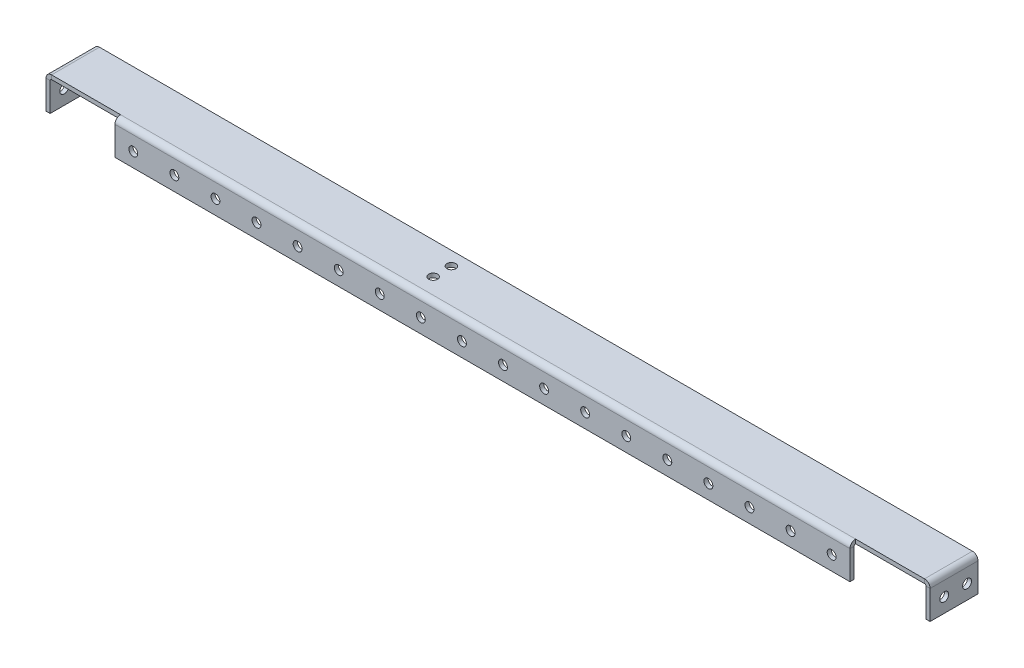
SolidWorks part; units mm, degrees
note: The reader was unsure of these and kept them because the rebuilt part matched: thickness of "Base-Flange1", "Edge-Flange2", "Edge-Flange3", "Edge-Flange1", "Sheet-Metal1", "Sheet-Metal2", "Sheet-Metal3", "Sheet-Metal4", "Sheet-Metal7", "Sheet-Metal8", "Sheet-Metal9", "Sheet-Metal10", "Sheet-Metal11"; flange length of "Edge-Flange2", "Edge-Flange3", "Edge-Flange1".
ref_plane "Front Plane" through (0, 0, 0) normal (0, 0, 1) x (1, 0, 0)
ref_plane "Top Plane" through (0, 0, 0) normal (0, 1, 0) x (1, 0, 0)
ref_plane "Right Plane" through (0, 0, 0) normal (1, 0, 0) x (0, 0, -1)
sketch "Sketch1" plane through (0, 0, 0) normal (0, 1, 0) x (1, 0, 0)
  line L1 (489.688, 0) -> (0, 0)
  line L2 (489.688, 0) -> (489.688, 26.67)
  line L3 (489.688, 26.67) -> (0, 26.67)
  line L4 (0, 0) -> (0, 26.67)
  point P0 (0, 0)
  dimension "D1" = 489.688
  dimension "D2" = 26.67
base flange "Base-Flange1" sketch "Sketch1" thickness 2.286 reverse thickness direction no parameters "D1"=0.8128
edge flange "Edge-Flange2" sketch "Sketch11" flange angle 90 flange length 19.05 flange position material inside bend radius 0.8128 thickness 2.286 relief rectangular parameters "D6"=10
sketch "Sketch11" plane through (0, -2.286, 0) normal (-1, 0, 0) x (0, 0, -1)
  line L0 (26.67, 0) -> (0, 0) construction
  line L1 (26.67, 0) -> (0, 0)
  line L2 (0, 0) -> (0, 16.764)
  line L3 (0, 16.764) -> (26.67, 16.764)
  line L4 (26.67, 16.764) -> (26.67, 0)
bend "EdgeBend2" bend radius 0.8128 bend angle 90 parameters "D5"=2
edge flange "Edge-Flange3" sketch "Sketch14" flange angle 90 flange length 19.05 flange position material outside bend radius 0.8128 thickness 2.286 relief rectangular parameters "D6"=10
sketch "Sketch14" plane through (489.688, -2.286, 0) normal (1, 0, 0) x (0, 0, 1)
  line L2 (-26.67, 0) -> (-26.67, 16.764)
  line L3 (-26.67, 16.764) -> (0, 16.764)
  line L4 (0, 16.764) -> (0, 0)
  line L7 (0, 0) -> (-26.67, 0) construction
  line L8 (0, 0) -> (-26.67, 0)
bend "EdgeBend3" bend radius 0.8128 bend angle 90 parameters "D5"=3
edge flange "Edge-Flange1" sketch "Sketch8" flange angle 90 flange length 19.05 flange position bend outside bend radius 0.8128 thickness 2.286 relief rectangular parameters "D6"=10
sketch "Sketch8" plane through (0, -2.286, 0) normal (0, 0, -1) x (1, 0, 0)
  line L0 (488.8752, 0) -> (3.0988, 0) construction
  line L2 (3.0988, 0) -> (3.0988, 16.764)
  line L3 (3.0988, 16.764) -> (488.8752, 16.764)
  line L4 (488.8752, 16.764) -> (488.8752, 0)
  line L5 (488.8752, 0) -> (3.0988, 0)
bend "EdgeBend1" bend radius 0.8128 bend angle 90 parameters "D5"=1
sketch "Sketch15" plane through (0, 0, 0.8128) normal (0, 0, -1) x (-1, 0, 0)
  line L0 (-488.8752, -19.05) -> (-3.0988, -19.05) construction
  line L1 (-59.436, -3.0988) -> (-21.336, -3.0988)
  line L2 (-59.436, -3.0988) -> (-59.436, -35.0012)
  line L3 (-59.436, -35.0012) -> (-21.336, -35.0012)
  line L4 (-21.336, -3.0988) -> (-21.336, -35.0012)
  line L5 (-59.436, -3.0988) -> (-21.336, -35.0012) construction
  line L6 (-59.436, -35.0012) -> (-21.336, -3.0988) construction
  line L7 (-488.8752, -3.0988) -> (-3.0988, -3.0988) construction
  line L8 (-2.286, -3.0988) -> (-2.286, -19.05) construction
  line L9 (-489.688, -19.05) -> (-489.688, -3.0988) construction
  line L10 (-479.528, -3.0988) -> (-441.428, -3.0988)
  line L11 (-479.528, -3.0988) -> (-479.528, -35.0012)
  line L12 (-479.528, -35.0012) -> (-441.428, -35.0012)
  line L13 (-441.428, -3.0988) -> (-441.428, -35.0012)
  line L14 (-479.528, -3.0988) -> (-441.428, -35.0012) construction
  line L15 (-479.528, -35.0012) -> (-441.428, -3.0988) construction
  point P0 (-40.386, -19.05)
  point P12 (-460.478, -19.05)
  dimension "D1" = 19.05
  dimension "D2" = 38.1
  dimension "D3" = 10.16
  dimension "D4" = 38.1
sketch "Sketch16" plane through (491.974, 0, 0) normal (1, 0, 0) x (0, 0, -1)
  line L0 (7.874, -11.0744) -> (33.274, -11.0744) construction
  line L2 (0, -3.0988) -> (0, -19.05) construction
  circle A0 centre (7.874, -11.0744) radius 2.4765
  circle A1 centre (20.574, -11.0744) radius 2.4765
  point P7 (0, -11.0744)
  dimension "D1" = 4.953
  dimension "D4" = 12.7
  dimension "D3" = 7.874
extrude "Cut-Extrude1" cut sketch "Sketch16" against normal through all normal cut yes
sketch "Sketch17" plane through (0, 0, 0.8128) normal (0, 0, -1) x (-1, 0, 0)
  line L1 (-3.0988, 0) -> (-41.4782, 0)
  line L2 (-3.0988, 0) -> (-3.0988, -19.05)
  line L3 (-3.0988, -19.05) -> (-41.4782, -19.05)
  line L4 (-41.4782, 0) -> (-41.4782, -19.05)
  line L5 (-488.8752, -19.05) -> (-3.0988, -19.05) construction
  line L6 (-3.0988, -19.05) -> (-3.0988, -3.0988) construction
  line L7 (-488.8752, -2.286) -> (-3.0988, -2.286) construction
  line L8 (-245.987, -2.286) -> (-245.987, -179.1808) construction
  line L9 (-488.8752, 0) -> (-488.8752, -19.05)
  line L10 (-450.4958, 0) -> (-450.4958, -19.05)
  line L11 (-488.8752, 0) -> (-450.4958, 0)
  line L12 (-488.8752, -19.05) -> (-450.4958, -19.05)
  line L13 (-488.8752, 0) -> (-3.0988, 0) construction
  point P10 (-245.987, -2.286)
  dimension "D1" = 38.3794
  dimension "D2" = 38.3794
extrude "Cut-Extrude2" cut sketch "Sketch17" along normal up to vertex (0.8128 mm away) and the other way blind 2.54 normal cut yes up to point (488.8752, -2.286, 0)
sketch "Sketch18" plane through (0, 0, 0.8128) normal (0, 0, -1) x (-1, 0, 0)
  line L0 (-245.987, -19.05) -> (-245.987, -3.0988) construction
  line L1 (-450.4958, -19.05) -> (-41.4782, -19.05) construction
  line L2 (-450.4958, -3.0988) -> (-41.4782, -3.0988) construction
  line L3 (-440.297, -11.0744) -> (-417.437, -11.0744) construction
  circle A0 centre (-440.297, -11.0744) radius 2.4765
  circle A1 centre (-417.437, -11.0744) radius 2.4765
  circle A2 centre (-394.577, -11.0744) radius 2.4765
  circle A3 centre (-371.717, -11.0744) radius 2.4765
  circle A4 centre (-348.857, -11.0744) radius 2.4765
  circle A5 centre (-325.997, -11.0744) radius 2.4765
  circle A6 centre (-303.137, -11.0744) radius 2.4765
  circle A7 centre (-280.277, -11.0744) radius 2.4765
  circle A8 centre (-257.417, -11.0744) radius 2.4765
  circle A9 centre (-234.557, -11.0744) radius 2.4765
  circle A10 centre (-211.697, -11.0744) radius 2.4765
  circle A11 centre (-188.837, -11.0744) radius 2.4765
  circle A12 centre (-165.977, -11.0744) radius 2.4765
  circle A13 centre (-143.117, -11.0744) radius 2.4765
  circle A14 centre (-120.257, -11.0744) radius 2.4765
  circle A21 centre (-97.397, -11.0744) radius 2.4765
  circle A22 centre (-74.537, -11.0744) radius 2.4765
  circle A23 centre (-51.677, -11.0744) radius 2.4765
  point P48 (-245.987, -11.0744)
  dimension "D1" = 4.953
  dimension "D3" = 22.86
  dimension "D2" = 18
extrude "Cut-Extrude3" cut sketch "Sketch18" against normal up to next normal cut yes
sketch "Sketch19" plane through (0, -2.286, 0) normal (0, -1, 0) x (1, 0, 0)
  circle A0 centre (206.5428, -19.0612) radius 2.4765
  circle A1 centre (206.5428, -8.9012) radius 2.4765
  circle A2 centre (206.5428, -8.9012) radius 2.4765 construction
  circle A3 centre (206.5428, -19.0612) radius 2.4765 construction
extrude "Cut-Extrude4" cut sketch "Sketch19" against normal up to next normal cut yes
sketch "Sketch20" plane through (0, 0, 0) normal (0, 1, 0) x (1, 0, 0)
  line L0 (108.1517, 31.2083) -> (133.9068, 10.2325)
  line L1 (133.9068, 10.2325) -> (142.0425, -15.3618)
  line L2 (142.0425, -15.3618) -> (163.021, -38.7726)
  line L3 (108.1517, 31.2083) -> (513.6538, 44.0224)
  line L4 (513.6538, 44.0224) -> (545.1159, -54.9552)
  line L5 (545.1159, -54.9552) -> (163.021, -38.7726)
extrude "Cut-Extrude5" [suppressed] cut sketch "Sketch20" against normal through all
sketch "Bend-Lines1" [suppressed] plane through (0, 0, 0) normal (0, 1, 0) x (1, 0, 0)
sketch "Bounding-Box1" [suppressed] plane through (0, 0, 0) normal (0, 1, 0) x (1, 0, 0)
sheet metal parameters "Sheet-Metal1" thickness 2.286 parameters "D1"=0.8128, "D7"=2.3622
flat pattern "Flat-Pattern1" [suppressed]
sketch "Bend-Lines2" plane through (0, 0, 0) normal (0, 1, 0) x (1, 0, 0)
sketch3d "Bounding-Box2" [suppressed]
  line L0 (489.688, 0, 0) -> (0, 0, 0) construction
  line L1 (489.688, 25.4, 0) -> (0, 25.4, 0) construction
  line L2 (489.688, 0, 0) -> (489.688, 25.4, 0) construction
  line L3 (0, 0, 0) -> (0, 25.4, 0) construction
sheet metal parameters "Sheet-Metal2" thickness 2.286 parameters "D1"=0.8128, "D7"=2.3622
flat pattern "Flat-Pattern1" [suppressed]
sketch "Bend-Lines2" plane through (0, 0, 0) normal (0, 1, 0) x (1, 0, 0)
  line L0 (-240.1218, -1909.4058) -> (242.484, -1909.4058) construction
  line L1 (-240.1218, -1909.4058) -> (242.484, -1909.4058) construction
  line L2 (245.2652, -1906.6246) -> (245.2652, -1868.5246) construction
  line L3 (-242.903, -1868.5246) -> (-242.903, -1906.6246) construction
  line L4 (245.2652, -1906.6246) -> (245.2652, -1868.5246) construction
  line L5 (-242.903, -1868.5246) -> (-242.903, -1906.6246) construction
sketch3d "Bounding-Box2" [suppressed]
  line L0 (262.3741, -1926.5147, 0) -> (-260.0119, -1926.5147, 0) construction
  line L1 (262.3741, -1868.5246, 0) -> (-260.0119, -1868.5246, 0) construction
  line L2 (262.3741, -1926.5147, 0) -> (262.3741, -1868.5246, 0) construction
  line L3 (-260.0119, -1926.5147, 0) -> (-260.0119, -1868.5246, 0) construction
bend of the flat pattern "Flatten-<EdgeBend1>1"
bend of the flat pattern "Flatten-<EdgeBend3>2"
bend of the flat pattern "Flatten-<EdgeBend2>2"
sketch "Sketch15-1" plane through (0, -2.3622, 1907.4647) normal (0, -1, 0) x (-1, 0, 0)
  line L1 (185.3318, -4.7222) -> (223.4318, -4.7222)
  line L2 (185.3318, -4.7222) -> (185.3318, -33.3778)
  line L3 (185.3318, -33.3778) -> (223.4318, -33.3778)
  line L4 (223.4318, -4.7222) -> (223.4318, -33.3778)
  line L5 (185.3318, -4.7222) -> (223.4318, -33.3778) construction
  line L6 (185.3318, -33.3778) -> (223.4318, -4.7222) construction
  line L8 (-262.3741, 38.9401) -> (260.0119, 38.9401) construction
  line L9 (-262.3741, 38.9401) -> (260.0119, 38.9401) construction
  line L10 (-234.684, -4.7222) -> (-196.584, -4.7222)
  line L11 (-234.684, -4.7222) -> (-234.684, -33.3778)
  line L12 (-234.684, -33.3778) -> (-196.584, -33.3778)
  line L13 (-196.584, -4.7222) -> (-196.584, -33.3778)
  line L14 (-234.684, -4.7222) -> (-196.584, -33.3778) construction
  line L15 (-234.684, -33.3778) -> (-196.584, -4.7222) construction
  point P0 (204.3818, -19.05)
  point P12 (-215.634, -19.05)
  dimension "D1" = 19.05
  dimension "D2" = 38.1
  dimension "D3" = 10.16
  dimension "D4" = 38.1
sketch "Sketch16-1" [suppressed] plane through (243.3241, 0, 0) normal (0, 1, 0) x (0, 0, -1)
  line L0 (-1900.2746, -12.7) -> (-1874.8746, -12.7) construction
  line L1 (-1906.6246, -19.05) -> (-1868.5246, -19.05) construction
  line L2 (-1906.6246, 0.8401) -> (-1906.6246, -19.05) construction
  circle A0 centre (-1900.2746, -12.7) radius 2.413
  circle A1 centre (-1887.5746, -12.7) radius 2.413
  circle A2 centre (-1874.8746, -12.7) radius 2.413
  dimension "D1" = 4.826
  dimension "D2" = 6.35
  dimension "D4" = 12.7
  dimension "D3" = 6.35
sheet metal parameters "Sheet-Metal3" thickness 2.286 parameters "D1"=0.8128, "D7"=2.3622
flat pattern "Flat-Pattern1"
sketch "Bend-Lines2" plane through (0, 0, 0) normal (0, 1, 0) x (1, 0, 0)
  line L2 (1.941, 25.4) -> (1.941, 0) construction
  line L3 (1.941, 25.4) -> (1.941, 0) construction
  point P0 (-255.27, -86.959)
  point P1 (255.27, -86.959)
sketch3d "Bounding-Box2" [suppressed]
  line L0 (489.688, 0, 0) -> (-15.1679, 0, 0) construction
  line L1 (489.688, 25.4, 0) -> (-15.1679, 25.4, 0) construction
  line L2 (489.688, 0, 0) -> (489.688, 25.4, 0) construction
  line L3 (-15.1679, 0, 0) -> (-15.1679, 25.4, 0) construction
bend of the flat pattern "Flatten-<EdgeBend2>1"
sheet metal parameters "Sheet-Metal4" thickness 2.286 parameters "D1"=0.8128, "D7"=2.3622
flat pattern "Flat-Pattern1"
sketch "Bend-Lines2" plane through (0, 0, 0) normal (0, 1, 0) x (1, 0, 0)
  line L2 (1.941, 25.4) -> (1.941, 0) construction
  line L3 (1.941, 25.4) -> (1.941, 0) construction
  line L4 (490.1092, 0) -> (490.1092, 25.4) construction
  line L5 (490.1092, 0) -> (490.1092, 25.4) construction
  point P0 (-244.844, -48.859)
  point P1 (244.844, -48.859)
sketch3d "Bounding-Box2" [suppressed]
  line L0 (507.2181, 0, 0) -> (-15.1679, 0, 0) construction
  line L1 (507.2181, 25.4, 0) -> (-15.1679, 25.4, 0) construction
  line L2 (507.2181, 0, 0) -> (507.2181, 25.4, 0) construction
  line L3 (-15.1679, 0, 0) -> (-15.1679, 25.4, 0) construction
bend of the flat pattern "Flatten-<EdgeBend2>1"
bend of the flat pattern "Flatten-<EdgeBend3>1"
sheet metal parameters "Sheet-Metal7" thickness 2.286 parameters "D1"=0.8128, "D7"=2.3622
flat pattern "Flat-Pattern1" [suppressed]
sketch "Bend-Lines2" plane through (0, 0, 0) normal (0, 1, 0) x (1, 0, 0)
  line L0 (4.7222, -2.7812) -> (487.328, -2.7812) construction
  line L1 (4.7222, -2.7812) -> (487.328, -2.7812) construction
  line L2 (490.1092, 0) -> (490.1092, 38.1) construction
  line L3 (1.941, 38.1) -> (1.941, 0) construction
  line L4 (490.1092, 0) -> (490.1092, 38.1) construction
  line L5 (1.941, 38.1) -> (1.941, 0) construction
sketch3d "Bounding-Box2" [suppressed]
  line L0 (507.2181, -19.8901, 0) -> (-15.1679, -19.8901, 0) construction
  line L1 (507.2181, 38.1, 0) -> (-15.1679, 38.1, 0) construction
  line L2 (507.2181, -19.8901, 0) -> (507.2181, 38.1, 0) construction
  line L3 (-15.1679, -19.8901, 0) -> (-15.1679, 38.1, 0) construction
bend of the flat pattern "Flatten-<EdgeBend1>1"
bend of the flat pattern "Flatten-<EdgeBend3>2"
bend of the flat pattern "Flatten-<EdgeBend2>2"
sketch "Sketch15-1" plane through (0, -2.3622, 0.8401) normal (0, -1, 0) x (-1, 0, 0)
  line L1 (-59.5122, -4.7222) -> (-21.4122, -4.7222)
  line L2 (-59.5122, -4.7222) -> (-59.5122, -33.3778)
  line L3 (-59.5122, -33.3778) -> (-21.4122, -33.3778)
  line L4 (-21.4122, -4.7222) -> (-21.4122, -33.3778)
  line L5 (-59.5122, -4.7222) -> (-21.4122, -33.3778) construction
  line L6 (-59.5122, -33.3778) -> (-21.4122, -4.7222) construction
  line L8 (-507.2181, 38.9401) -> (15.1679, 38.9401) construction
  line L9 (-507.2181, 38.9401) -> (15.1679, 38.9401) construction
  line L10 (-479.528, -4.7222) -> (-441.428, -4.7222)
  line L11 (-479.528, -4.7222) -> (-479.528, -33.3778)
  line L12 (-479.528, -33.3778) -> (-441.428, -33.3778)
  line L13 (-441.428, -4.7222) -> (-441.428, -33.3778)
  line L14 (-479.528, -4.7222) -> (-441.428, -33.3778) construction
  line L15 (-479.528, -33.3778) -> (-441.428, -4.7222) construction
  point P0 (-40.4622, -19.05)
  point P12 (-460.478, -19.05)
  dimension "D1" = 19.05
  dimension "D2" = 38.1
  dimension "D3" = 10.16
  dimension "D4" = 38.1
sketch "Sketch16-1" plane through (488.1681, 0, 0) normal (0, 1, 0) x (0, 0, -1)
  line L0 (6.35, -12.7) -> (31.75, -12.7) construction
  line L1 (0, -19.05) -> (38.1, -19.05) construction
  line L2 (0, 0.8401) -> (0, -19.05) construction
  circle A0 centre (6.35, -12.7) radius 2.413
  circle A1 centre (19.05, -12.7) radius 2.413
  circle A2 centre (31.75, -12.7) radius 2.413
  dimension "D1" = 4.826
  dimension "D2" = 6.35
  dimension "D4" = 12.7
  dimension "D3" = 6.35
sheet metal parameters "Sheet-Metal8" thickness 2.286 parameters "D1"=0.8128, "D7"=2.3622
flat pattern "Flat-Pattern1" [suppressed]
sketch "Bend-Lines2" plane through (0, 0, 0) normal (0, 1, 0) x (1, 0, 0)
  line L0 (41.4782, -1.3027) -> (450.4958, -1.3027) construction
  line L1 (41.4782, -1.3027) -> (450.4958, -1.3027) construction
  line L2 (490.1779, 0) -> (490.1779, 25.4) construction
  line L3 (1.7961, 25.4) -> (1.7961, 0) construction
  line L4 (490.1779, 0) -> (490.1779, 25.4) construction
  line L5 (1.7961, 25.4) -> (1.7961, 0) construction
sketch3d "Bounding-Box2" [suppressed]
  line L0 (507.4318, -18.5566, 0) -> (-15.4578, -18.5566, 0) construction
  line L1 (507.4318, 25.4, 0) -> (-15.4578, 25.4, 0) construction
  line L2 (507.4318, -18.5566, 0) -> (507.4318, 25.4, 0) construction
  line L3 (-15.4578, -18.5566, 0) -> (-15.4578, 25.4, 0) construction
bend of the flat pattern "Flatten-<EdgeBend1>1"
bend of the flat pattern "Flatten-<EdgeBend3>2"
bend of the flat pattern "Flatten-<EdgeBend2>2"
sketch "Sketch15-1" plane through (0, -2.286, -0.4934) normal (0, -1, 0) x (-1, 0, 0)
  line L1 (-59.436, -3.0988) -> (-21.336, -3.0988)
  line L2 (-59.436, -3.0988) -> (-59.436, -35.0012)
  line L3 (-59.436, -35.0012) -> (-21.336, -35.0012)
  line L4 (-21.336, -3.0988) -> (-21.336, -35.0012)
  line L5 (-59.436, -3.0988) -> (-21.336, -35.0012) construction
  line L6 (-59.436, -35.0012) -> (-21.336, -3.0988) construction
  line L8 (-507.4318, 24.9066) -> (15.4578, 24.9066) construction
  line L9 (-507.4318, 24.9066) -> (15.4578, 24.9066) construction
  line L10 (-479.528, -3.0988) -> (-441.428, -3.0988)
  line L11 (-479.528, -3.0988) -> (-479.528, -35.0012)
  line L12 (-479.528, -35.0012) -> (-441.428, -35.0012)
  line L13 (-441.428, -3.0988) -> (-441.428, -35.0012)
  line L14 (-479.528, -3.0988) -> (-441.428, -35.0012) construction
  line L15 (-479.528, -35.0012) -> (-441.428, -3.0988) construction
  point P0 (-40.386, -19.05)
  point P12 (-460.478, -19.05)
  dimension "D1" = 19.05
  dimension "D2" = 38.1
  dimension "D3" = 10.16
  dimension "D4" = 38.1
sketch "Sketch16-1" plane through (488.3818, 0, 0) normal (0, 1, 0) x (0, 0, -1)
  line L0 (6.35, -12.7) -> (31.75, -12.7) construction
  line L1 (0, -19.05) -> (25.4, -19.05) construction
  line L2 (0, 37.886) -> (0, -19.05) construction
  circle A0 centre (6.35, -12.7) radius 2.413
  circle A1 centre (19.05, -12.7) radius 2.413
  circle A2 centre (31.75, -12.7) radius 2.413
  dimension "D1" = 4.826
  dimension "D2" = 6.35
  dimension "D4" = 12.7
  dimension "D3" = 6.35
sheet metal parameters "Sheet-Metal9" thickness 2.286 parameters "D1"=0.8128, "D7"=2.3622
flat pattern "Flat-Pattern1" [suppressed]
sketch "Bend-Lines2" plane through (0, 0, 0) normal (0, 1, 0) x (1, 0, 0)
  line L0 (41.4782, -1.3027) -> (450.4958, -1.3027) construction
  line L1 (41.4782, -1.3027) -> (450.4958, -1.3027) construction
  line L2 (490.1779, 0) -> (490.1779, 26.67) construction
  line L3 (1.7961, 26.67) -> (1.7961, 0) construction
  line L4 (490.1779, 0) -> (490.1779, 26.67) construction
  line L5 (1.7961, 26.67) -> (1.7961, 0) construction
sketch3d "Bounding-Box2" [suppressed]
  line L0 (507.4318, -18.5566, 0) -> (-15.4578, -18.5566, 0) construction
  line L1 (507.4318, 26.67, 0) -> (-15.4578, 26.67, 0) construction
  line L2 (507.4318, -18.5566, 0) -> (507.4318, 26.67, 0) construction
  line L3 (-15.4578, -18.5566, 0) -> (-15.4578, 26.67, 0) construction
bend of the flat pattern "Flatten-<EdgeBend1>1"
bend of the flat pattern "Flatten-<EdgeBend3>2"
bend of the flat pattern "Flatten-<EdgeBend2>2"
sketch "Sketch15-1" plane through (0, -2.286, -0.4934) normal (0, -1, 0) x (-1, 0, 0)
  line L1 (-59.436, -3.0988) -> (-21.336, -3.0988)
  line L2 (-59.436, -3.0988) -> (-59.436, -35.0012)
  line L3 (-59.436, -35.0012) -> (-21.336, -35.0012)
  line L4 (-21.336, -3.0988) -> (-21.336, -35.0012)
  line L5 (-59.436, -3.0988) -> (-21.336, -35.0012) construction
  line L6 (-59.436, -35.0012) -> (-21.336, -3.0988) construction
  line L8 (-507.4318, 26.1766) -> (15.4578, 26.1766) construction
  line L9 (-507.4318, 26.1766) -> (15.4578, 26.1766) construction
  line L10 (-479.528, -3.0988) -> (-441.428, -3.0988)
  line L11 (-479.528, -3.0988) -> (-479.528, -35.0012)
  line L12 (-479.528, -35.0012) -> (-441.428, -35.0012)
  line L13 (-441.428, -3.0988) -> (-441.428, -35.0012)
  line L14 (-479.528, -3.0988) -> (-441.428, -35.0012) construction
  line L15 (-479.528, -35.0012) -> (-441.428, -3.0988) construction
  point P0 (-40.386, -19.05)
  point P12 (-460.478, -19.05)
  dimension "D1" = 19.05
  dimension "D2" = 38.1
  dimension "D3" = 10.16
  dimension "D4" = 38.1
sketch "Sketch16-1" plane through (488.3818, 0, 0) normal (0, 1, 0) x (0, 0, -1)
  line L0 (7.874, -11.0744) -> (33.274, -11.0744) construction
  line L2 (0, 37.886) -> (0, 21.9348) construction
  circle A0 centre (7.874, -11.0744) radius 2.4765
  circle A1 centre (20.574, -11.0744) radius 2.4765
  dimension "D1" = 4.953
  dimension "D4" = 12.7
  dimension "D3" = 7.874
sheet metal parameters "Sheet-Metal10" thickness 2.286 parameters "D1"=0.8128, "D7"=2.3622
flat pattern "Flat-Pattern1" [suppressed]
sketch "Bend-Lines2" plane through (0, 0, 0) normal (0, 1, 0) x (1, 0, 0)
  line L0 (41.4782, -1.3027) -> (450.4958, -1.3027) construction
  line L1 (41.4782, -1.3027) -> (450.4958, -1.3027) construction
  line L2 (490.1779, 0) -> (490.1779, 26.67) construction
  line L3 (1.7961, 26.67) -> (1.7961, 0) construction
  line L4 (490.1779, 0) -> (490.1779, 26.67) construction
  line L5 (1.7961, 26.67) -> (1.7961, 0) construction
sketch3d "Bounding-Box2" [suppressed]
  line L0 (507.4318, -18.5566, 0) -> (-15.4578, -18.5566, 0) construction
  line L1 (507.4318, 26.67, 0) -> (-15.4578, 26.67, 0) construction
  line L2 (507.4318, -18.5566, 0) -> (507.4318, 26.67, 0) construction
  line L3 (-15.4578, -18.5566, 0) -> (-15.4578, 26.67, 0) construction
bend of the flat pattern "Flatten-<EdgeBend1>1"
bend of the flat pattern "Flatten-<EdgeBend3>2"
bend of the flat pattern "Flatten-<EdgeBend2>2"
sketch "Sketch15-1" plane through (0, -2.286, -0.4934) normal (0, -1, 0) x (-1, 0, 0)
  line L1 (-59.436, -3.0988) -> (-21.336, -3.0988)
  line L2 (-59.436, -3.0988) -> (-59.436, -35.0012)
  line L3 (-59.436, -35.0012) -> (-21.336, -35.0012)
  line L4 (-21.336, -3.0988) -> (-21.336, -35.0012)
  line L5 (-59.436, -3.0988) -> (-21.336, -35.0012) construction
  line L6 (-59.436, -35.0012) -> (-21.336, -3.0988) construction
  line L8 (-507.4318, 26.1766) -> (15.4578, 26.1766) construction
  line L9 (-507.4318, 26.1766) -> (15.4578, 26.1766) construction
  line L10 (-479.528, -3.0988) -> (-441.428, -3.0988)
  line L11 (-479.528, -3.0988) -> (-479.528, -35.0012)
  line L12 (-479.528, -35.0012) -> (-441.428, -35.0012)
  line L13 (-441.428, -3.0988) -> (-441.428, -35.0012)
  line L14 (-479.528, -3.0988) -> (-441.428, -35.0012) construction
  line L15 (-479.528, -35.0012) -> (-441.428, -3.0988) construction
  point P0 (-40.386, -19.05)
  point P12 (-460.478, -19.05)
  dimension "D1" = 19.05
  dimension "D2" = 38.1
  dimension "D3" = 10.16
  dimension "D4" = 38.1
sketch "Sketch16-1" plane through (488.3818, 0, 0) normal (0, 1, 0) x (0, 0, -1)
  line L0 (7.874, -11.0744) -> (33.274, -11.0744) construction
  line L2 (0, 37.886) -> (0, 21.9348) construction
  circle A0 centre (7.874, -11.0744) radius 2.4765
  circle A1 centre (20.574, -11.0744) radius 2.4765
  dimension "D1" = 4.953
  dimension "D4" = 12.7
  dimension "D3" = 7.874
sheet metal parameters "Sheet-Metal11" thickness 2.286 parameters "D1"=0.8128, "D7"=2.3622
flat pattern "Flat-Pattern1" [suppressed]
sketch "Bend-Lines2" plane through (0, 0, 0) normal (0, 1, 0) x (1, 0, 0)
  line L0 (41.4782, -1.3027) -> (137.2886, -1.3027) construction
  line L1 (41.4782, -1.3027) -> (137.2886, -1.3027) construction
  line L3 (1.7961, 26.67) -> (1.7961, 0) construction
  line L5 (1.7961, 26.67) -> (1.7961, 0) construction
  point P2 (490.1779, 0)
  point P3 (490.1779, 26.67)
sketch3d "Bounding-Box2" [suppressed]
  line L0 (-15.4578, -18.5566, 0) -> (138.1444, -18.5566, 0) construction
  line L1 (-15.4578, 26.67, 0) -> (138.1444, 26.67, 0) construction
  line L2 (-15.4578, -18.5566, 0) -> (-15.4578, 26.67, 0) construction
  line L3 (138.1444, -18.5566, 0) -> (138.1444, 26.67, 0) construction
bend of the flat pattern "Flatten-<EdgeBend1>1"
bend of the flat pattern "Flatten-<EdgeBend2>2"
sketch "Sketch15-1" plane through (0, -2.286, -0.4934) normal (0, -1, 0) x (-1, 0, 0)
  line L1 (-59.436, -3.0988) -> (-21.336, -3.0988)
  line L2 (-59.436, -3.0988) -> (-59.436, -35.0012)
  line L3 (-59.436, -35.0012) -> (-21.336, -35.0012)
  line L4 (-21.336, -3.0988) -> (-21.336, -35.0012)
  line L5 (-59.436, -3.0988) -> (-21.336, -35.0012) construction
  line L6 (-59.436, -35.0012) -> (-21.336, -3.0988) construction
  line L8 (-113.7241, 26.1766) -> (15.4578, 26.1766) construction
  line L9 (-489.688, -19.05) -> (-489.688, -3.0988) construction
  line L10 (-479.528, -3.0988) -> (-441.428, -3.0988)
  line L11 (-479.528, -3.0988) -> (-479.528, -35.0012)
  line L12 (-479.528, -35.0012) -> (-441.428, -35.0012)
  line L13 (-441.428, -3.0988) -> (-441.428, -35.0012)
  line L14 (-479.528, -3.0988) -> (-441.428, -35.0012) construction
  line L15 (-479.528, -35.0012) -> (-441.428, -3.0988) construction
  point P0 (-40.386, -19.05)
  point P12 (-460.478, -19.05)
  dimension "D1" = 19.05
  dimension "D2" = 38.1
  dimension "D3" = 10.16
  dimension "D4" = 38.1
sketch "Sketch16-1" plane through (491.974, 0, 0) normal (1, 0, 0) x (0, 0, -1)
  line L0 (7.874, -11.0744) -> (33.274, -11.0744) construction
  line L2 (0, 37.886) -> (0, 21.9348)
  circle A0 centre (7.874, -11.0744) radius 2.4765
  circle A1 centre (20.574, -11.0744) radius 2.4765
  dimension "D1" = 4.953
  dimension "D4" = 12.7
  dimension "D3" = 7.874
equation "\"D1@Sketch17\"=\"D2@Sketch17\""
